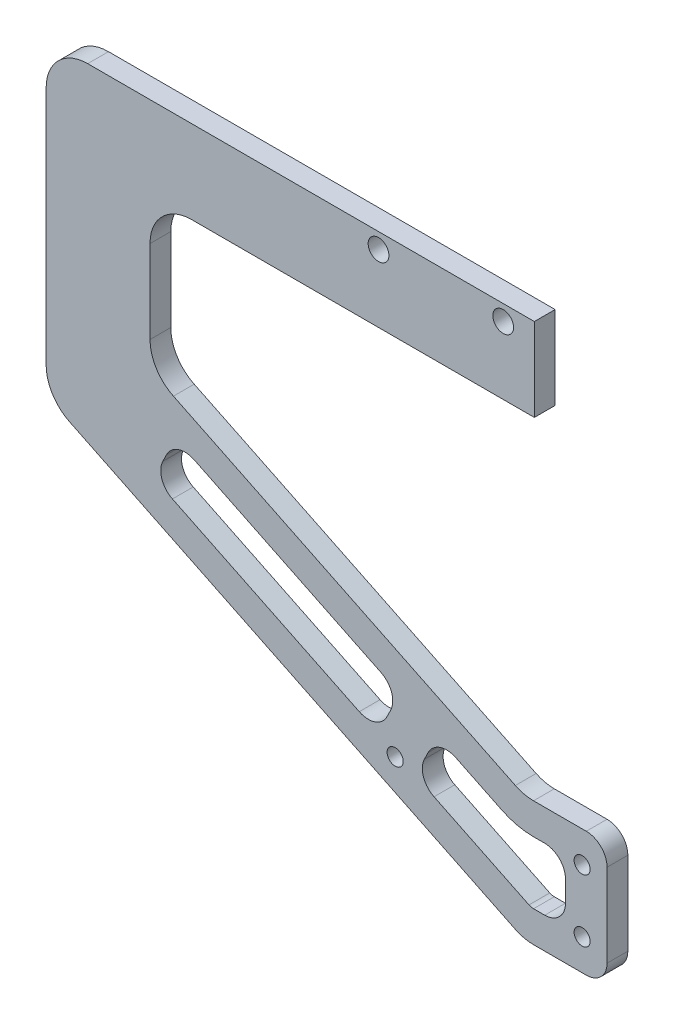
SolidWorks part; units mm, degrees
material "6061 Alloy"
ref_plane "Front Plane" through (0, 0, 0) normal (0, 0, 1) x (1, 0, 0)
ref_plane "Top Plane" through (0, 0, 0) normal (0, 1, 0) x (1, 0, 0)
ref_plane "Right Plane" through (0, 0, 0) normal (1, 0, 0) x (0, 0, -1)
sketch "Sketch1" plane through (0, 0, 0) normal (0, 0, 1) x (1, 0, 0)
  line L0 (0, 0) -> (0, 38.1)
  line L1 (0, 38.1) -> (-25.4, 38.1)
  line L2 (-139.7, 101.6) -> (-139.7, 127)
  line L3 (-127, 139.7) -> (-22.225, 139.7)
  line L4 (-22.225, 139.7) -> (-22.225, 165.1)
  line L5 (-22.225, 165.1) -> (-158.75, 165.1)
  line L6 (-171.45, 152.4) -> (-171.45, 78.9311)
  line L7 (0, 0) -> (-25.4, 0)
  line L8 (-164.3015, 67.5087) -> (-25.4, 0)
  line L9 (0, 19.05) -> (25.4, 19.05) construction
  line L10 (25.4, 19.05) -> (25.4, 120.65) construction
  line L11 (25.4, 120.65) -> (-127, 120.65) construction
  line L12 (-25.4, 38.1) -> (-132.5515, 90.1776)
  line L13 (0, 19.05) -> (-7.62, 19.05) construction
  line L14 (-7.62, 28.575) -> (-7.62, 9.525) construction
  line L15 (-7.62, 28.575) -> (-64.77, 28.575) construction
  line L16 (-69.85, 160.3375) -> (-31.75, 160.3375) construction
  line L17 (-50.8, 160.3375) -> (-50.8, 120.65) construction
  line L18 (-127, 120.65) -> (-127, 101.6) construction
  arc A0 (-171.45, 78.9311) -> (-164.3015, 67.5087) centre (-158.75, 78.9311) ccw
  arc A1 (-158.75, 165.1) -> (-171.45, 152.4) centre (-158.75, 152.4) ccw
  arc A2 (-139.7, 127) -> (-127, 139.7) centre (-127, 127) cw
  arc A3 (-132.5515, 90.1776) -> (-139.7, 101.6) centre (-127, 101.6) cw
  circle A7 centre (-31.75, 160.3375) radius 3.175 construction
  circle A8 centre (-69.85, 160.3375) radius 3.175 construction
  point P26 (-50.8, 160.3375)
  point P28 (-50.8, 120.65)
  dimension "D9" = 12.7
  dimension "D10" = 12.7
  dimension "D22" = 6.35
  dimension "D1" = 38.1
  dimension "D3" = 31.75
  dimension "D4" = 25.4
  dimension "D5" = 19.05
  dimension "D6" = 19.05
  dimension "D7" = 57.15
  dimension "D11" = 25.4
  dimension "D12" = 101.6
  dimension "D13" = 152.4
  dimension "D14" = 25.4
  dimension "D15" = 19.05
  dimension "D17" = 7.62
  dimension "D19" = 4.7625
  dimension "D20" = 38.1
  dimension "D21" = 9.525
extrude "Boss-Extrude1" add sketch "Sketch1" along normal blind 6.35
hole_wizard "1/4 (0.25) Diameter Hole1" positions "Sketch3" profile "Sketch2" hole size "1/4" standard "ANSI Inch"
sketch "Sketch3" plane through (0, 0, 6.35) normal (0, 0, 1) x (1, 0, 0)
  line L0 (-69.85, 160.3375) -> (-22.225, 160.3375) construction
  line L1 (-22.225, 139.7) -> (-22.225, 165.1) construction
  line L3 (-22.225, 165.1) -> (-158.75, 165.1) construction
  point P4 (-69.85, 160.3375)
  point P6 (-31.75, 160.3375)
  dimension "D1" = 9.525
  dimension "D2" = 38.1
  dimension "D3" = 4.7625
sketch "Sketch2" plane through (-69.85, 160.3375, 6.35) normal (1, 0, 0) x (0, -1, 0)
  line L0 (0, 0) -> (0, 11.5597)
  line L1 (0, 11.5597) -> (3.175, 9.652)
  line L2 (3.175, 9.652) -> (3.175, 0)
  line L5 (3.175, 0) -> (0, 0)
  line L10 (0, 11.5597) -> (-3.175, 9.652) construction
  line L11 (0, -6.35) -> (0, 107.95) construction
  dimension "Hole Dia." = 6.35
  dimension "Hole Depth" = 9.652
  dimension "Drill Angle" = 118
hole_wizard "#10 (0.1935) Diameter Hole1" positions "Sketch5" profile "Sketch4" hole size "#10" standard "ANSI Inch"
sketch "Sketch5" plane through (0, 0, 6.35) normal (0, 0, 1) x (1, 0, 0)
  line L0 (-7.62, 28.575) -> (-7.62, 9.525) construction
  line L2 (0, 19.05) -> (-7.62, 19.05) construction
  line L3 (0, 0) -> (0, 38.1) construction
  line L6 (-64.77, 28.575) -> (-7.62, 28.575) construction
  point P0 (-7.62, 28.575)
  point P2 (-7.62, 9.525)
  point P18 (-64.77, 28.575)
  dimension "D1" = 19.05
  dimension "D2" = 7.62
  dimension "D3" = 57.15
sketch "Sketch4" plane through (-7.62, 28.575, 6.35) normal (1, 0, 0) x (0, -1, 0)
  line L0 (0, 0) -> (0, 11.1286)
  line L1 (0, 11.1286) -> (2.4574, 9.652)
  line L2 (2.4574, 9.652) -> (2.4574, 0)
  line L5 (2.4574, 0) -> (0, 0)
  line L10 (0, 11.1286) -> (-2.4575, 9.652) construction
  line L11 (0, -6.35) -> (0, 107.95) construction
  dimension "Hole Dia." = 4.9149
  dimension "Hole Depth" = 9.652
  dimension "Drill Angle" = 118
fillet "Fillet1" radius 12.7 2 edges at (-25.4, 0, 3.175) (-25.4, 38.1, 3.175)
fillet "Fillet2" radius 6.35 2 edges at (0, 0, 3.175) (0, 38.1, 3.175)
sketch "Sketch6" plane through (0, 0, 6.35) normal (0, 0, 1) x (1, 0, 0)
  line L0 (-75.9984, 161.925) -> (-158.75, 161.925)
  line L1 (-25.4, 161.925) -> (-158.75, 161.925) construction
  line L2 (-29.0004, 161.925) -> (-34.4996, 161.925)
  line L3 (-37.8984, 161.925) -> (-63.7016, 161.925)
  line L4 (-25.4, 142.875) -> (-25.4, 161.925) construction
  line L5 (-65.4189, 22.9801) -> (-26.6409, 4.1332)
  line L6 (-162.9136, 70.3643) -> (-26.6409, 4.1332) construction
  line L7 (-3.175, 6.35) -> (-3.175, 31.75) construction
  line L10 (-22.4772, 0) -> (-6.35, 0)
  line L11 (0, 6.35) -> (0, 31.75)
  line L12 (-6.35, 38.1) -> (-22.4772, 38.1)
  line L13 (-28.0287, 39.3776) -> (-132.5515, 90.1776)
  line L14 (-139.7, 101.6) -> (-139.7, 127)
  line L15 (-127, 139.7) -> (-22.225, 139.7)
  line L16 (-22.225, 139.7) -> (-22.225, 165.1)
  line L17 (-22.225, 165.1) -> (-158.75, 165.1)
  line L18 (-171.45, 152.4) -> (-171.45, 78.9311)
  line L19 (-164.3015, 67.5087) -> (-28.0287, 1.2776)
  line L20 (-22.4772, 0) -> (-6.35, 0)
  line L21 (0, 6.35) -> (0, 31.75)
  line L22 (-6.35, 38.1) -> (-22.4772, 38.1)
  line L23 (-28.0287, 39.3776) -> (-132.5515, 90.1776)
  line L24 (-139.7, 101.6) -> (-139.7, 127)
  line L25 (-127, 139.7) -> (-22.225, 139.7)
  line L26 (-22.225, 139.7) -> (-22.225, 165.1)
  line L27 (-22.225, 165.1) -> (-158.75, 165.1)
  line L28 (-171.45, 152.4) -> (-171.45, 78.9311)
  line L29 (-164.3015, 67.5087) -> (-28.0287, 1.2776)
  line L31 (-168.275, 152.4) -> (-168.275, 78.9311)
  line L32 (-162.9136, 70.3643) -> (-68.7684, 24.608)
  line L33 (-22.4772, 3.175) -> (-6.35, 3.175)
  line L34 (-3.175, 12.9843) -> (-3.175, 25.1157)
  line L35 (-6.35, 34.925) -> (-22.4772, 34.925)
  line L36 (-29.4166, 36.522) -> (-133.9394, 87.322)
  line L37 (-142.875, 101.6) -> (-142.875, 127)
  line L38 (-127, 142.875) -> (-25.4, 142.875)
  line L39 (-25.4, 142.875) -> (-25.4, 160.3375)
  circle A0 centre (-64.77, 28.575) radius 2.4574 construction
  circle A1 centre (-7.62, 28.575) radius 2.4574 construction
  circle A2 centre (-7.62, 9.525) radius 2.4574 construction
  circle A3 centre (-31.75, 160.3375) radius 3.175 construction
  arc A8 (-6.35, 0) -> (0, 6.35) centre (-6.35, 6.35) ccw
  arc A9 (0, 31.75) -> (-6.35, 38.1) centre (-6.35, 31.75) ccw
  arc A10 (-28.0287, 39.3776) -> (-22.4772, 38.1) centre (-22.4772, 50.8) ccw
  arc A11 (-139.7, 101.6) -> (-132.5515, 90.1776) centre (-127, 101.6) ccw
  arc A12 (-127, 139.7) -> (-139.7, 127) centre (-127, 127) ccw
  arc A13 (-158.75, 165.1) -> (-171.45, 152.4) centre (-158.75, 152.4) ccw
  arc A14 (-171.45, 78.9311) -> (-164.3015, 67.5087) centre (-158.75, 78.9311) ccw
  arc A15 (-28.0287, 1.2776) -> (-22.4772, 0) centre (-22.4772, 12.7) ccw
  arc A16 (-6.35, 0) -> (0, 6.35) centre (-6.35, 6.35) ccw
  arc A17 (0, 31.75) -> (-6.35, 38.1) centre (-6.35, 31.75) ccw
  arc A18 (-28.0287, 39.3776) -> (-22.4772, 38.1) centre (-22.4772, 50.8) ccw
  arc A19 (-139.7, 101.6) -> (-132.5515, 90.1776) centre (-127, 101.6) ccw
  arc A20 (-127, 139.7) -> (-139.7, 127) centre (-127, 127) ccw
  arc A21 (-158.75, 165.1) -> (-171.45, 152.4) centre (-158.75, 152.4) ccw
  arc A22 (-171.45, 78.9311) -> (-164.3015, 67.5087) centre (-158.75, 78.9311) ccw
  arc A23 (-28.0287, 1.2776) -> (-22.4772, 0) centre (-22.4772, 12.7) ccw
  arc A24 (-158.75, 161.925) -> (-168.275, 152.4) centre (-158.75, 152.4) ccw
  arc A25 (-168.275, 78.9311) -> (-162.9136, 70.3643) centre (-158.75, 78.9311) ccw
  arc A26 (-26.6409, 4.1332) -> (-22.4772, 3.175) centre (-22.4772, 12.7) ccw
  arc A27 (-6.35, 3.175) -> (-3.175, 6.35) centre (-6.35, 6.35) ccw
  arc A28 (-3.1895, 32.0528) -> (-6.35, 34.925) centre (-6.35, 31.75) ccw
  arc A29 (-29.4166, 36.522) -> (-22.4772, 34.925) centre (-22.4772, 50.8) ccw
  arc A30 (-142.875, 101.6) -> (-133.9394, 87.322) centre (-127, 101.6) ccw
  arc A31 (-127, 142.875) -> (-142.875, 127) centre (-127, 127) ccw
  circle A32 centre (-31.75, 160.3375) radius 3.175
  circle A34 centre (-69.85, 160.3375) radius 6.35
  arc A35 (-75.9984, 161.925) -> (-63.7016, 161.925) centre (-69.85, 160.3375) ccw
  circle A43 centre (-7.62, 9.525) radius 2.4574
  circle A44 centre (-64.77, 28.575) radius 2.4574
  circle A45 centre (-7.62, 28.575) radius 2.4574
  arc A46 (-65.4189, 22.9801) -> (-68.7684, 24.608) centre (-64.77, 28.575) ccw
  arc A47 (-3.1895, 32.0528) -> (-3.175, 25.1157) centre (-7.62, 28.575) ccw
  arc A48 (-3.175, 12.9843) -> (-3.1895, 6.0472) centre (-7.62, 9.525) ccw
  arc A49 (-37.8984, 161.925) -> (-25.4, 160.3375) centre (-31.75, 160.3375) ccw
  circle A50 centre (-64.77, 28.575) radius 5.6324 construction
  circle A51 centre (-31.75, 160.3375) radius 6.35 construction
  circle A52 centre (-7.62, 9.525) radius 5.6324 construction
  circle A53 centre (-7.62, 28.575) radius 5.6324 construction
  arc A54 (-3.175, 31.75) -> (-6.35, 34.925) centre (-6.35, 31.75) ccw construction
  dimension "D1" = 0
  dimension "D2" = 3.175
  dimension "D3" = 3.175
  dimension "D4" = 3.175
extrude "Cut-Extrude1" [suppressed] cut sketch "Sketch6" against normal blind 3.175 contours A49 L3 A35 L0 A24 L31 A25 L32 A46 L5 A26 L33 A27 A48 L34 A47 A28 L35 A29 L36 A30 L37 A31 L38 L39
sketch "Sketch7" plane through (0, 0, 6.35) normal (0, 0, 1) x (1, 0, 0)
  line L0 (-12.7, 28.575) -> (-22.4772, 28.575)
  line L1 (-32.1924, 30.8108) -> (-51.9549, 40.4158)
  line L2 (-58.6067, 26.7295) -> (-23.8651, 9.8444)
  line L3 (-22.4772, 9.525) -> (-12.7, 9.525)
  line L4 (-12.7, 28.575) -> (-12.7, 9.525)
  line L5 (-58.6067, 26.7295) -> (-51.9549, 40.4158)
  line L6 (-32.1924, 30.8108) -> (-136.7151, 81.6108) construction
  line L7 (-160.1379, 76.0755) -> (-23.8651, 9.8444) construction
  line L8 (-22.4772, 9.525) -> (-6.35, 9.525) construction
  line L9 (-6.35, 28.575) -> (-22.4772, 28.575) construction
  line L10 (-22.4772, 0) -> (-6.35, 0)
  line L11 (0, 6.35) -> (0, 31.75)
  line L12 (-6.35, 38.1) -> (-22.4772, 38.1)
  line L13 (-28.0287, 39.3776) -> (-132.5515, 90.1776)
  line L14 (-139.7, 101.6) -> (-139.7, 127)
  line L15 (-127, 139.7) -> (-22.225, 139.7)
  line L16 (-22.225, 139.7) -> (-22.225, 165.1)
  line L17 (-22.225, 165.1) -> (-158.75, 165.1)
  line L18 (-171.45, 152.4) -> (-171.45, 78.9311)
  line L19 (-164.3015, 67.5087) -> (-28.0287, 1.2776)
  line L20 (-162.6009, 128.2776) -> (-162.6009, 90.1776)
  line L21 (0, 6.35) -> (0, 31.75) construction
  line L22 (-162.6009, 90.1776) -> (-145.4765, 90.1776)
  line L23 (-145.4765, 90.1776) -> (-145.4765, 128.2776)
  line L24 (-139.7, 101.6) -> (-139.7, 127) construction
  line L25 (-127, 139.7) -> (-22.225, 139.7) construction
  line L26 (-22.225, 139.7) -> (-22.225, 165.1) construction
  line L27 (-22.225, 165.1) -> (-158.75, 165.1) construction
  line L28 (-171.45, 152.4) -> (-171.45, 78.9311) construction
  line L29 (-145.4765, 128.2776) -> (-162.6009, 128.2776)
  line L30 (-139.7, 160.9809) -> (-139.7, 144.1002)
  line L31 (-139.7, 144.1002) -> (-79.038, 144.1002)
  line L32 (-79.038, 144.1002) -> (-79.038, 160.9809)
  line L33 (-28.0287, 39.3776) -> (-132.5515, 90.1776) construction
  line L34 (-28.0287, 39.3776) -> (-132.5515, 90.1776)
  line L35 (-79.038, 160.9809) -> (-139.7, 160.9809)
  line L36 (-28.0287, 39.3776) -> (-132.5515, 90.1776) construction
  line L37 (-164.3015, 67.5087) -> (-28.0287, 1.2776) construction
  line L38 (-22.4772, 0) -> (-6.35, 0) construction
  line L39 (-6.35, 38.1) -> (-22.4772, 38.1) construction
  line L40 (-61.6368, 160.9809) -> (-61.6368, 144.1002)
  line L41 (-61.6368, 144.1002) -> (-38.9837, 144.1002)
  line L42 (-38.9837, 144.1002) -> (-38.9837, 160.9809)
  line L43 (-38.9837, 160.9809) -> (-61.6368, 160.9809)
  line L49 (-131.9116, 79.2762) -> (-63.3773, 45.9673)
  line L50 (-63.3773, 45.9673) -> (-70.0291, 32.281)
  line L51 (-70.0291, 32.281) -> (-138.5634, 65.5899)
  line L52 (-138.5634, 65.5899) -> (-131.9116, 79.2762)
  line L53 (-164.3015, 67.5087) -> (-28.0287, 1.2776) construction
  line L54 (-58.6067, 26.7295) -> (-70.0291, 32.281) construction
  line L55 (-64.77, 28.575) -> (-53.5025, 51.7583) construction
  arc A0 (-32.1924, 30.8108) -> (-22.4772, 28.575) centre (-22.4772, 50.8) ccw
  arc A1 (-23.8651, 9.8444) -> (-22.4772, 9.525) centre (-22.4772, 12.7) ccw
  arc A8 (-6.35, 0) -> (0, 6.35) centre (-6.35, 6.35) ccw
  arc A9 (0, 31.75) -> (-6.35, 38.1) centre (-6.35, 31.75) ccw
  arc A10 (-28.0287, 39.3776) -> (-22.4772, 38.1) centre (-22.4772, 50.8) ccw
  arc A11 (-139.7, 101.6) -> (-132.5515, 90.1776) centre (-127, 101.6) ccw
  arc A12 (-127, 139.7) -> (-139.7, 127) centre (-127, 127) ccw
  arc A13 (-158.75, 165.1) -> (-171.45, 152.4) centre (-158.75, 152.4) ccw
  arc A14 (-171.45, 78.9311) -> (-164.3015, 67.5087) centre (-158.75, 78.9311) ccw
  arc A15 (-28.0287, 1.2776) -> (-22.4772, 0) centre (-22.4772, 12.7) ccw
  arc A16 (-6.35, 0) -> (0, 6.35) centre (-6.35, 6.35) ccw construction
  arc A17 (0, 31.75) -> (-6.35, 38.1) centre (-6.35, 31.75) ccw construction
  arc A18 (-28.0287, 39.3776) -> (-22.4772, 38.1) centre (-22.4772, 50.8) ccw construction
  arc A19 (-139.7, 101.6) -> (-132.5515, 90.1776) centre (-127, 101.6) ccw construction
  arc A20 (-127, 139.7) -> (-139.7, 127) centre (-127, 127) ccw construction
  arc A21 (-158.75, 165.1) -> (-171.45, 152.4) centre (-158.75, 152.4) ccw construction
  arc A22 (-171.45, 78.9311) -> (-164.3015, 67.5087) centre (-158.75, 78.9311) ccw construction
  arc A23 (-28.0287, 1.2776) -> (-22.4772, 0) centre (-22.4772, 12.7) ccw construction
  point P46 (-64.3179, 29.5052)
  dimension "D3" = 9.525
  dimension "D4" = 9.525
  dimension "D5" = 12.7
  dimension "D6" = 12.7
  dimension "D7" = 76.2
  dimension "D8" = 38.1
  dimension "D1" = 0
  dimension "D2" = 9.525
extrude "Cut-Extrude2" cut sketch "Sketch7" against normal up to next contours L52 L51 L50 L49 | L5 L1 A0 L0 L4 L3 A1 L2 region at (-100.9704, 55.7786, 6.35)
fillet "Fillet3" radius 6.35 8 edges at (-12.7, 9.525, 3.175) (-58.6067, 26.7295, 3.175) (-12.7, 28.575, 3.175) (-51.9549, 40.4158, 3.175) (-138.5634, 65.5899, 3.175) (-70.0291, 32.281, 3.175) (-63.3773, 45.9673, 3.175) (-131.9116, 79.2762, 3.175)
